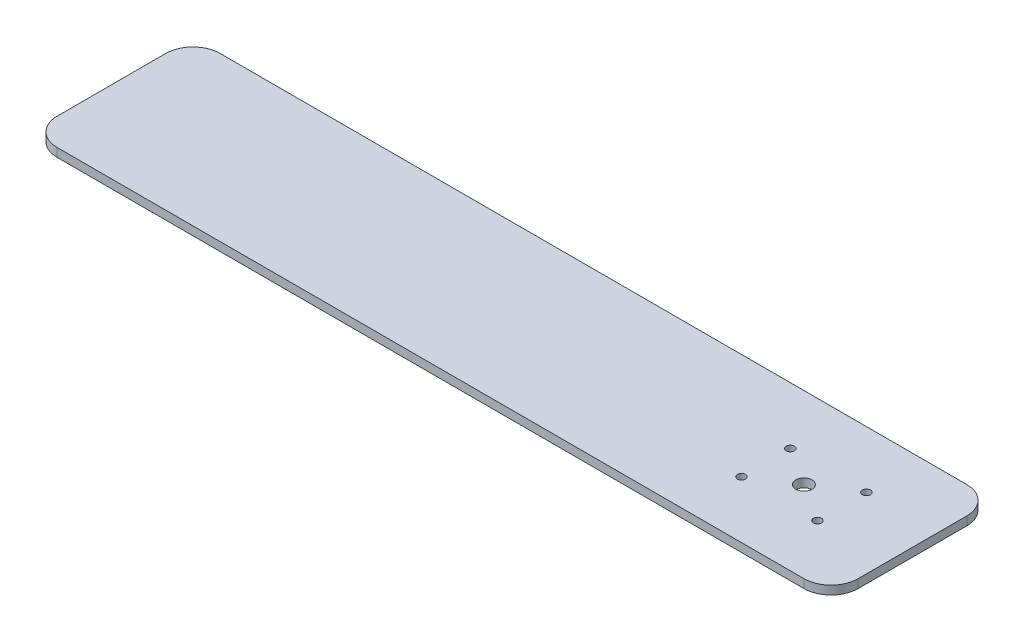
SolidWorks part; units mm, degrees
ref_plane "Front Plane" through (0, 0, 0) normal (0, 0, 1) x (1, 0, 0)
ref_plane "Top Plane" through (0, 0, 0) normal (0, 1, 0) x (1, 0, 0)
ref_plane "Right Plane" through (0, 0, 0) normal (1, 0, 0) x (0, 0, -1)
sketch "Sketch1" plane through (0, 0, 0) normal (0, 1, 0) x (1, 0, 0)
  line L0 (-55, 0) -> (0, 0) construction
  line L1 (-55, 30) -> (240, 30)
  line L2 (-55, 30) -> (-55, -30)
  line L3 (-55, -30) -> (240, -30)
  line L4 (240, 30) -> (240, -30)
  point P7 (200, 0)
  dimension "D1" = 60
  dimension "D2" = 55
  dimension "D3" = 200
  dimension "D4" = 40
extrude "Boss-Extrude1" add sketch "Sketch1" along normal blind 3.175
fillet "Fillet1" radius 10 4 edges at (-55, 1.5875, 30) (-55, 1.5875, -30) (240, 1.5875, 30) (240, 1.5875, -30)
hole_wizard "Ø6.0mm Dowel Hole1" positions "Sketch2" profile "Sketch3" hole size "Ø6.0" standard "DIN" end condition up to next
sketch "Sketch2" plane through (0, 3.175, 0) normal (0, 1, 0) x (1, 0, 0)
  point P0 (200, 0)
  dimension "D1" = 200
sketch "Sketch3" plane through (200, 3.175, 0) normal (1, 0, 0) x (0, 0, 1)
  line L0 (0, 0) -> (0, 3.175)
  line L1 (0, 3.175) -> (3, 3.175)
  line L2 (3, 3.175) -> (3, 0)
  line L5 (3, 0) -> (0, 0)
  line L11 (0, -6.35) -> (0, 107.95) construction
  dimension "Thru Hole Dia." = 6
  dimension "Thru Hole Depth" = 3.175
hole_wizard "Ø3.0mm Dowel Hole1" positions "Sketch4" profile "Sketch5" hole size "Ø3.0" standard "ANSI Metric" end condition up to next
sketch "Sketch4" plane through (0, 3.175, 0) normal (0, 1, 0) x (1, 0, 0)
  line L0 (214, -9) -> (186, -9) construction
  line L1 (214, -9) -> (214, 9) construction
  circle A0 centre (200, 0) radius 3 construction
  point P0 (214, -9)
  point P7 (186, -9)
  point P8 (186, 9)
  point P9 (214, 9)
  point P15 (0, 0)
  dimension "D3" = 28
  dimension "D4" = 18
  dimension "D5" = 14
  dimension "D6" = 9
  dimension "D1" = 2
  dimension "D2" = 2
sketch "Sketch5" plane through (214, 3.175, 9) normal (1, 0, 0) x (0, 0, 1)
  line L0 (0, 0) -> (0, 3.175)
  line L1 (0, 3.175) -> (1.5, 3.175)
  line L2 (1.5, 3.175) -> (1.5, 0)
  line L5 (1.5, 0) -> (0, 0)
  line L11 (0, -6.35) -> (0, 107.95) construction
  dimension "Thru Hole Dia." = 3
  dimension "Thru Hole Depth" = 3.175
equation "\"Pivot to Pivot Dist\"= 200"
equation "\"D3@Sketch1\"=\"Pivot to Pivot Dist\""
equation "\"D1@Sketch2\"=\"Pivot to Pivot Dist\""
